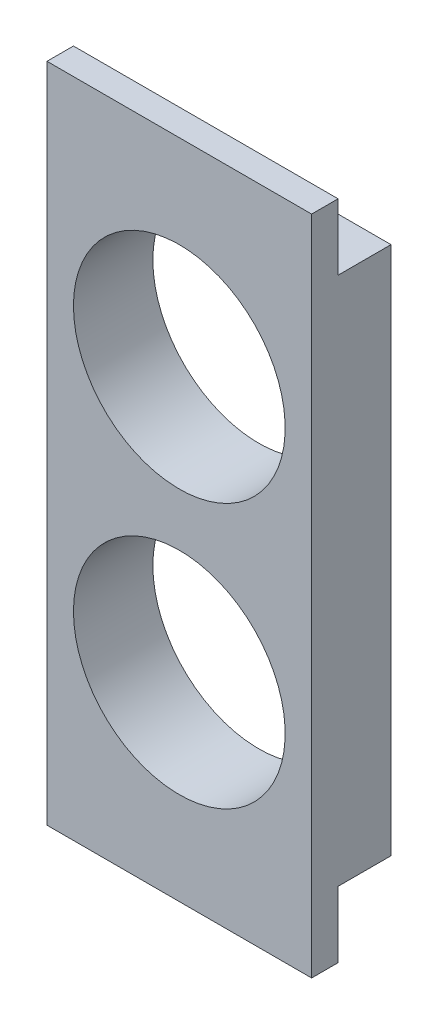
SolidWorks part; units mm, degrees
ref_plane "前视基准面" through (0, 0, 0) normal (0, 0, 1) x (1, 0, 0)
ref_plane "上视基准面" through (0, 0, 0) normal (0, 1, 0) x (1, 0, 0)
ref_plane "右视基准面" through (0, 0, 0) normal (1, 0, 0) x (0, 0, -1)
sketch "草图1" plane through (0, 0, 0) normal (0, 0, 1) x (1, 0, 0)
  line L0 (0, 100) -> (0, -100) construction
  line L1 (50, -100) -> (-50, -100)
  line L2 (50, -100) -> (50, 100)
  line L3 (50, 100) -> (-50, 100)
  line L4 (-50, -100) -> (-50, 100)
  line L5 (50, -100) -> (-50, 100) construction
  line L6 (50, 100) -> (-50, -100) construction
  line L7 (-50, 0) -> (50, 0) construction
  circle A0 centre (0, 50) radius 40
  circle A1 centre (0, -50) radius 40
  point P0 (0, 0)
  dimension "D3" = 80
  dimension "D1" = 100
  dimension "D2" = 200
  dimension "D4" = 50
extrude "凸台-拉伸1" add sketch "草图1" along normal blind 20
sketch "草图2" plane through (0, 0, 20) normal (0, 0, 1) x (1, 0, 0)
  line L0 (-50, 100) -> (-50, -100) construction
  line L1 (50, -125) -> (-50, -125)
  line L2 (50, -125) -> (50, 125)
  line L3 (50, 125) -> (-50, 125)
  line L4 (-50, -125) -> (-50, 125)
  line L5 (50, -125) -> (-50, 125) construction
  line L6 (50, 125) -> (-50, -125) construction
  point P0 (0, 0)
  dimension "D1" = 250
extrude "凸台-拉伸2" add sketch "草图2" along normal blind 10
sketch "草图3" plane through (0, 0, 20) normal (0, 0, -1) x (-1, 0, 0)
  circle A1 centre (0, 50) radius 40
  circle A2 centre (0, 50) radius 40
  circle A3 centre (0, -50) radius 40
  circle A4 centre (0, -50) radius 40
  dimension "D1" = 0
  dimension "D2" = 0
extrude "切除-拉伸1" cut sketch "草图3" against normal through all
sketch "草图4" plane through (0, 100, 0) normal (0, 1, 0) x (1, 0, 0)
  line L0 (50, 0) -> (50, -20) construction
  line L1 (50, -10) -> (25.1207, -10) construction
  line L2 (-50, -20) -> (-50, 0) construction
  circle A0 centre (-40, -10) radius 5
  point P6 (0, 0)
  dimension "D1" = 10
  dimension "D2" = 10
extrude "切除-拉伸2" cut sketch "草图4" against normal blind 20
